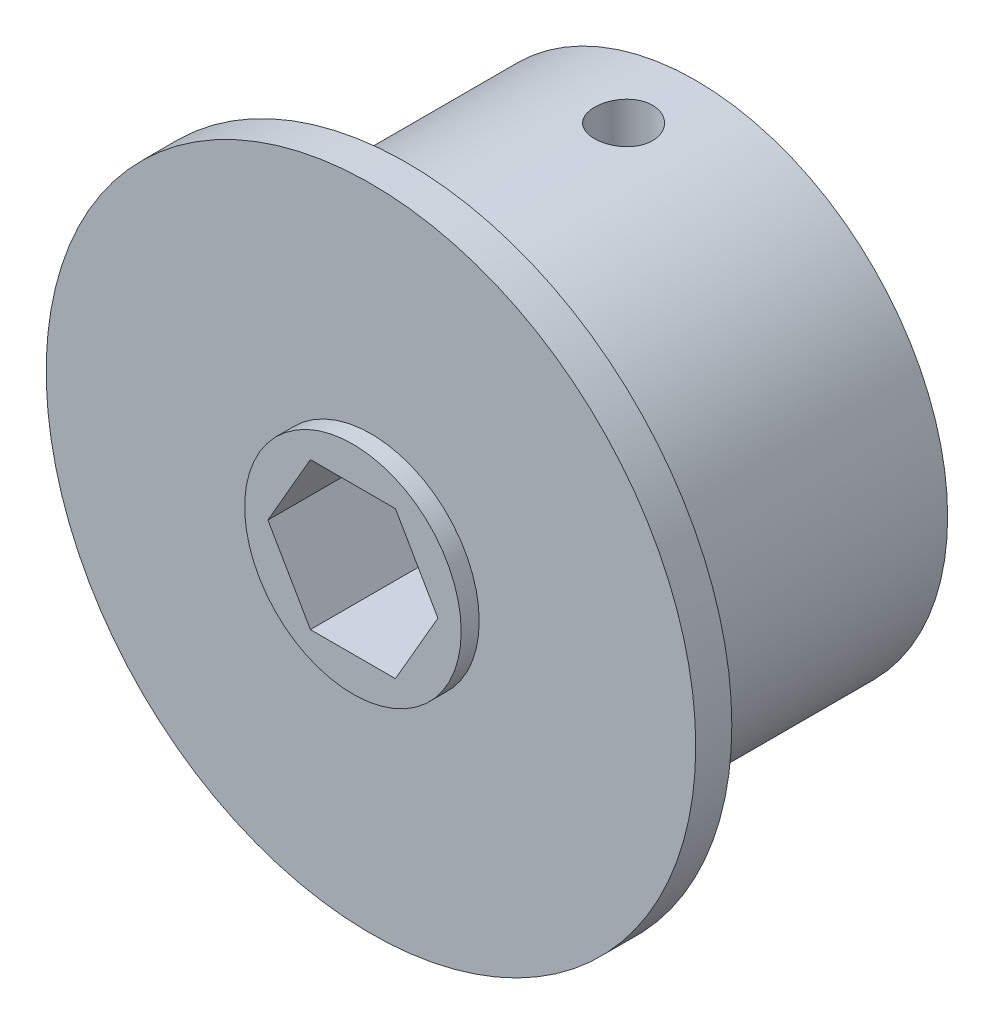
SolidWorks part; units mm, degrees
material "PET"
ref_plane "Front Plane" through (0, 0, 0) normal (0, 0, 1) x (1, 0, 0)
ref_plane "Top Plane" through (0, 0, 0) normal (0, 1, 0) x (1, 0, 0)
ref_plane "Right Plane" through (0, 0, 0) normal (1, 0, 0) x (0, 0, -1)
sketch "Sketch1" plane through (0, 0, 0) normal (0, 0, 1) x (1, 0, 0)
  line L1 (7.479, 0) -> (3.7395, 6.477)
  line L2 (3.7395, 6.477) -> (-3.7395, 6.477)
  line L3 (-3.7395, 6.477) -> (-7.479, 0)
  line L4 (-7.479, 0) -> (-3.7395, -6.477)
  line L5 (-3.7395, -6.477) -> (3.7395, -6.477)
  line L6 (3.7395, -6.477) -> (7.479, 0)
  circle A0 centre (0, 0) radius 22.1615
  circle A1 centre (0, 0) radius 6.477 construction
  dimension "D1" = 44.323
  dimension "D2" = 12.954
extrude "Boss-Extrude1" add sketch "Sketch1" along normal blind 12.7
sketch "Sketch2" plane through (0, 0, 12.7) normal (0, 0, 1) x (1, 0, 0)
  line L0 (3.7395, -6.477) -> (7.479, 0) construction
  line L1 (7.479, 0) -> (3.7395, 6.477)
  line L2 (3.7395, 6.477) -> (-3.7395, 6.477)
  line L3 (-3.7395, 6.477) -> (-7.479, 0)
  line L4 (-7.479, 0) -> (-3.7395, -6.477)
  line L5 (-3.7395, -6.477) -> (3.7395, -6.477)
  line L6 (3.7395, -6.477) -> (7.479, 0)
  circle A0 centre (0, 0) radius 28.575
  circle A1 centre (0, 0) radius 6.477 construction
  dimension "D1" = 57.15
extrude "Boss-Extrude2" add sketch "Sketch2" along normal blind 3.175
sketch "Sketch3" plane through (0, 0, 0) normal (0, 0, -1) x (-1, 0, 0)
  circle A0 centre (0, 0) radius 22.1615
  dimension "D1" = 44.323
extrude "Boss-Extrude3" add sketch "Sketch3" along normal blind 12.7
sketch "Sketch4" plane through (0, 0, 0) normal (0, 1, 0) x (1, 0, 0)
  circle A0 centre (0, 6.35) radius 2.5527
  dimension "D1" = 5.1054
  dimension "D2" = 6.35
extrude "Cut-Extrude1" cut sketch "Sketch4" against normal through all both and the other way through all
sketch "Sketch5" plane through (0, 0, 15.875) normal (0, 0, 1) x (1, 0, 0)
  line L0 (3.7395, -6.477) -> (7.479, 0) construction
  line L1 (7.479, 0) -> (3.7395, 6.477)
  line L2 (3.7395, 6.477) -> (-3.7395, 6.477)
  line L3 (-3.7395, 6.477) -> (-7.479, 0)
  line L4 (-7.479, 0) -> (-3.7395, -6.477)
  line L5 (-3.7395, -6.477) -> (3.7395, -6.477)
  line L6 (3.7395, -6.477) -> (7.479, 0)
  line L7 (3.7395, -6.477) -> (7.479, 0) construction
  circle A0 centre (0, 0) radius 9.525
  circle A1 centre (0, 0) radius 6.477 construction
  dimension "D1" = 19.05
extrude "Boss-Extrude4" add sketch "Sketch5" along normal blind 1.5875
